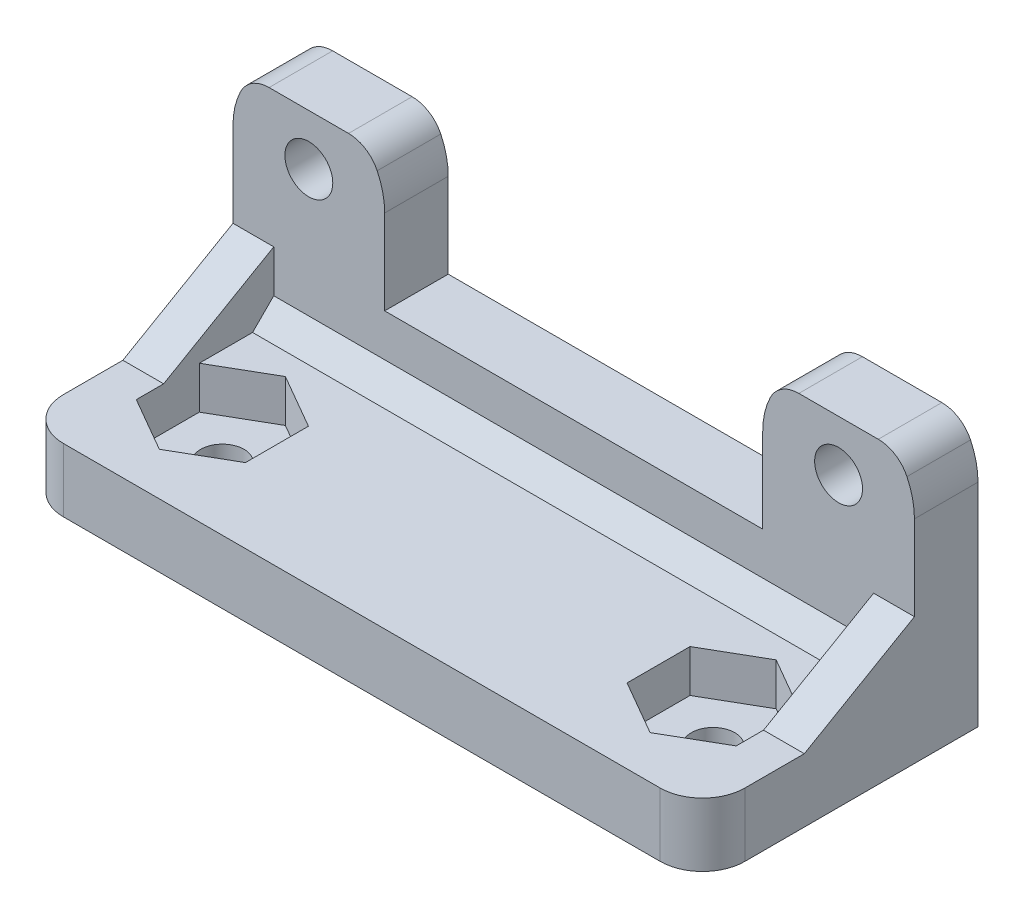
SolidWorks part; units mm, degrees
material "ABS"
ref_plane "Front Plane" through (0, 0, 0) normal (0, 0, 1) x (1, 0, 0)
ref_plane "Top Plane" through (0, 0, 0) normal (0, 1, 0) x (1, 0, 0)
ref_plane "Right Plane" through (0, 0, 0) normal (1, 0, 0) x (0, 0, -1)
sketch "Sketch1" plane through (0, 0, 0) normal (0, 0, 1) x (1, 0, 0)
  line L0 (-12.5, 0) -> (12.5, 0) construction
  line L1 (8.9205, 0) -> (16.0795, 0)
  line L2 (-16.0795, 0) -> (-8.9205, 0)
  line L3 (-16.0795, 0) -> (-16.0795, -10)
  line L4 (-16.0795, -10) -> (16.0795, -10)
  line L5 (16.0795, 0) -> (16.0795, -10)
  line L6 (-8.9205, 0) -> (-8.9205, -4)
  line L7 (-8.9205, -4) -> (8.9205, -4)
  line L8 (8.9205, -4) -> (8.9205, 0)
  circle A0 centre (12.5, 0) radius 1.0795
  circle A1 centre (-12.5, 0) radius 1.0795
  circle A2 centre (-12.5, 0) radius 3.5795
  circle A3 centre (12.5, 0) radius 3.5795
  point P4 (0, 0)
  dimension "D2" = 2.159
  dimension "D3" = 2.5
  dimension "D1" = 25
  dimension "D4" = 4
  dimension "D5" = 10
extrude "Boss-Extrude1" add sketch "Sketch1" along normal blind 3 contours A3 L8 L7 L6 A2 L3 L4 L5 | A2 | A3 region at (0, -6.6869, 0)
sketch "Sketch2" plane through (0, 0, 0) normal (0, 0, 1) x (1, 0, 0)
  line L1 (-16.0795, -10) -> (16.0795, -10)
  line L2 (-16.0795, -10) -> (-16.0795, -7)
  line L3 (-16.0795, -7) -> (16.0795, -7)
  line L4 (16.0795, -10) -> (16.0795, -7)
  line L5 (-16.0795, -10) -> (16.0795, -10) construction
  line L6 (-16.0795, 0) -> (-16.0795, -10) construction
  point P6 (0, -7)
  dimension "D1" = 3
  dimension "D2" = 0
extrude "Boss-Extrude2" add sketch "Sketch2" along normal blind 10 and the other way up to surface from surface other way up to face at (0, -2.6051, 0) starting at face at (0, -2.6051, 3)
sketch "Sketch3" plane through (0, -7, 0) normal (0, 1, 0) x (1, 0, 0)
  line L0 (-11.5795, -8) -> (11.5795, -8) construction
  line L1 (16.0795, -13) -> (-16.0795, -13) construction
  line L2 (-16.0795, -3) -> (-16.0795, -13) construction
  point P2 (0, -8)
  dimension "D1" = 23.159
  dimension "D2" = 5
  dimension "D3" = 4.5
sketch "Sketch4" plane through (0, 0, 0) normal (0, 0, -1) x (-1, 0, 0)
  point P0 (12.5, 0)
  point P3 (-12.5, 0)
hole_wizard "#4-40 Tapped Hole1" positions "Sketch4" profile "Sketch5" tap size "#4-40" standard "ANSI Inch" end condition through all
sketch "Sketch5" plane through (-12.5, 0, 0) normal (1, 0, 0) x (0, 1, 0)
  line L0 (0, 0) -> (0, 13)
  line L1 (0, 13) -> (1.1303, 13)
  line L2 (1.1303, 13) -> (1.1303, 0)
  line L5 (1.1303, 0) -> (0, 0)
  line L11 (0, -6.35) -> (0, 107.95) construction
  dimension "Thru Tap Drill Dia." = 2.2606
  dimension "Thru Tap Drill Depth" = 13
sketch "Sketch6" plane through (0, -7, 0) normal (0, 1, 0) x (1, 0, 0)
  point P0 (-11.5795, -8)
  point P3 (11.5795, -8)
hole_wizard "M2.5x0.45 Tapped Hole1" positions "Sketch6" profile "Sketch7" tap size "M2.5x0.45" standard "ANSI Metric" end condition through all
sketch "Sketch7" plane through (-11.5795, -7, 8) normal (1, 0, 0) x (0, 0, 1)
  line L0 (0, 0) -> (0, 3)
  line L1 (0, 3) -> (1.025, 3)
  line L2 (1.025, 3) -> (1.025, 0)
  line L5 (1.025, 0) -> (0, 0)
  line L11 (0, -6.35) -> (0, 107.95) construction
  dimension "Thru Tap Drill Dia." = 2.05
  dimension "Thru Tap Drill Depth" = 3
sketch "Sketch9" plane through (0, -7, 0) normal (0, 1, 0) x (1, 0, 0)
  line L1 (-9.0045, -6.5133) -> (-11.5795, -5.0266)
  line L2 (-11.5795, -5.0266) -> (-14.1545, -6.5133)
  line L3 (-14.1545, -6.5133) -> (-14.1545, -9.4867)
  line L4 (-14.1545, -9.4867) -> (-11.5795, -10.9734)
  line L5 (-11.5795, -10.9734) -> (-9.0045, -9.4867)
  line L6 (-9.0045, -9.4867) -> (-9.0045, -6.5133)
  line L8 (11.5795, -5.0266) -> (9.0045, -6.5133)
  line L9 (9.0045, -6.5133) -> (9.0045, -9.4867)
  line L10 (9.0045, -9.4867) -> (11.5795, -10.9734)
  line L11 (11.5795, -10.9734) -> (14.1545, -9.4867)
  line L12 (14.1545, -9.4867) -> (14.1545, -6.5133)
  line L13 (14.1545, -6.5133) -> (11.5795, -5.0266)
  circle A0 centre (-11.5795, -8) radius 2.575 construction
  circle A1 centre (11.5795, -8) radius 2.575 construction
  dimension "D1" = 5.15
extrude "Cut-Extrude1" cut sketch "Sketch9" against normal blind 2 and the other way through all
fillet "Fillet1" radius 2 2 edges at (16.0795, -8.5, 13) (-16.0795, -8.5, 13)
ref_plane "Plane1" through (-12.5, 0, 0) normal (-1, 0, 0) x (0, 0, 1)
sketch "Sketch8" plane through (-16.0795, 0, 0) normal (-1, 0, 0) x (0, 0, 1)
  line L0 (3, -4) -> (8.1962, -7)
  line L1 (3, 0) -> (3, -7) construction
  line L2 (3, -7) -> (11, -7) construction
  dimension "D1" = 30
  dimension "D2" = 3
rib "Rib1" sketch "Sketch8" sketch "Sketch8" thickness 1.925 extrusion direction parallel to sketch draft on no parameters "D1"=1.925
mirror "Mirror1" about plane through (0, 0, 0) normal (1, 0, 0) of "Rib1"
chamfer "Chamfer1" distance 1 angle 45 1 edges at (0, -7, 3)
sketch "Sketch10" plane through (0, 0, 3) normal (0, 0, 1) x (1, 0, 0)
  line L0 (15.1557, 2.4) -> (9.8443, 2.4)
  line L1 (-15.1557, 2.4) -> (-9.8443, 2.4)
  arc A0 (16.0795, 0) -> (8.9205, 0) centre (12.5, 0) ccw construction
  arc A1 (-8.9205, 0) -> (-16.0795, 0) centre (-12.5, 0) ccw construction
  circle A2 centre (12.5, 0) radius 1.1303 construction
  arc M8 (16.0795, 0) -> (8.9205, 0) centre (12.5, 0) ccw
  arc M12 (-8.9205, 0) -> (-16.0795, 0) centre (-12.5, 0) ccw
  dimension "D1" = 2.4
extrude "Cut-Extrude2" cut sketch "Sketch10" against normal through all contours L0 M8 | L1 M12 region at (12.5, 2.8792, 3) region at (-12.5, 2.8792, 3)
fillet "Fillet2" radius 1.5 4 edges at (15.1557, 2.4, 1.5) (9.8443, 2.4, 1.5) (-9.8443, 2.4, 1.5) (-15.1557, 2.4, 1.5)
